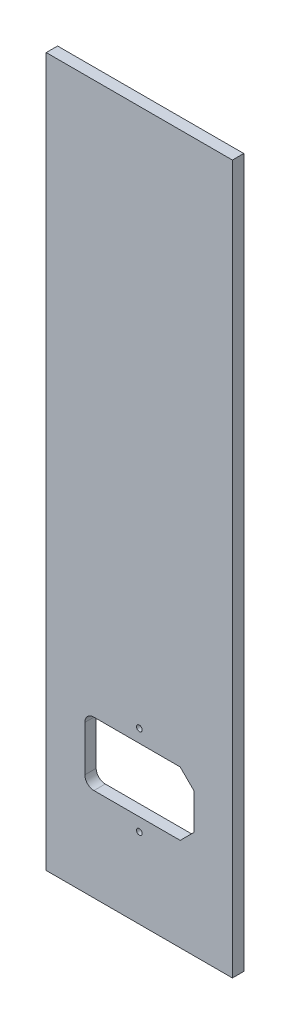
SolidWorks part; units mm, degrees
ref_plane "Front Plane" through (0, 0, 0) normal (0, 0, 1) x (1, 0, 0)
ref_plane "Top Plane" through (0, 0, 0) normal (0, 1, 0) x (1, 0, 0)
ref_plane "Right Plane" through (0, 0, 0) normal (1, 0, 0) x (0, 0, -1)
sketch "Sketch1" plane through (0, 0, 0) normal (0, 0, 1) x (1, 0, 0)
  line L1 (-41, -156) -> (41, -156)
  line L2 (-41, -156) -> (-41, 156)
  line L3 (-41, 156) -> (41, 156)
  line L4 (41, -156) -> (41, 156)
  line L5 (-41, -156) -> (41, 156) construction
  line L6 (-41, 156) -> (41, -156) construction
  point P0 (0, 0)
  dimension "D1" = 312
  dimension "D2" = 82
extrude "Boss-Extrude1" add sketch "Sketch1" along normal blind 5
sketch "Sketch2" plane through (0, 0, 5) normal (0, 0, 1) x (1, 0, 0)
  line L0 (0, -1000) -> (0, 49000) construction
  line L1 (-24, -115) -> (24, -115)
  line L2 (-24, -115) -> (-24, -87)
  line L3 (-24, -87) -> (24, -87)
  line L4 (24, -115) -> (24, -87)
  line L5 (-24, -115) -> (24, -87) construction
  line L6 (-24, -87) -> (24, -115) construction
  line L7 (-41, -156) -> (41, -156) construction
  circle A0 centre (0, -81.25) radius 1.25
  circle A1 centre (0, -120.75) radius 1.25
  point P0 (0, -101)
  dimension "D6" = 2.5
  dimension "D7" = 2.5
  dimension "D1" = 28
  dimension "D2" = 48
  dimension "D3" = 55
  dimension "D4" = 19.75
  dimension "D5" = 19.75
extrude "Cut-Extrude1" cut sketch "Sketch2" against normal blind 10
chamfer "Chamfer1" distance 6 angle 45 2 edges at (24, -115, 2.5) (24, -87, 2.5)
fillet "Fillet1" radius 4 2 edges at (-24, -115, 2.5) (-24, -87, 2.5)
